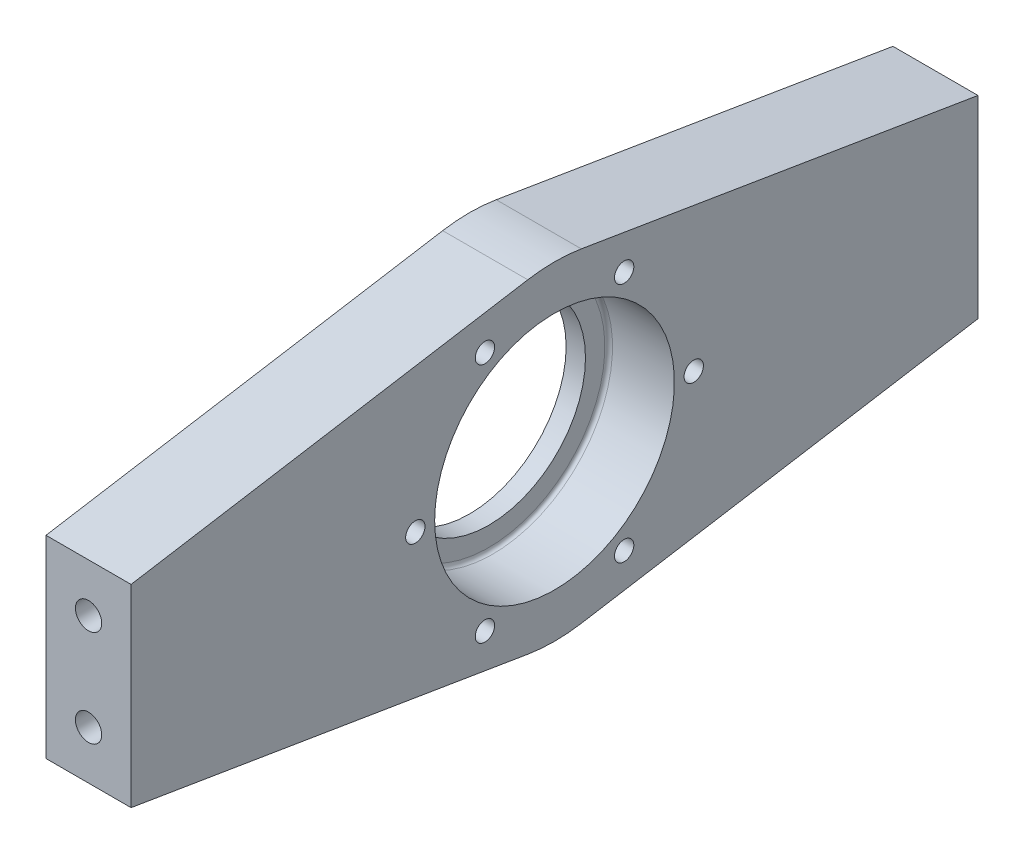
SolidWorks part; units mm, degrees
material "PA38 (3.3206)"
ref_plane "Płaszczyzna przednia" through (0, 0, 0) normal (0, 0, 1) x (1, 0, 0)
ref_plane "Płaszczyzna górna" through (0, 0, 0) normal (0, 1, 0) x (1, 0, 0)
ref_plane "Płaszczyzna prawa" through (0, 0, 0) normal (1, 0, 0) x (0, 0, -1)
sketch "Szkic1" plane through (0, 0, 0) normal (0, 0, 1) x (1, 0, 0)
  line L0 (-11, 0) -> (11, 0) construction
  line L1 (-11, 25) -> (-11, 42.5)
  line L2 (-11, 42.5) -> (11, 42.5)
  line L3 (11, 42.5) -> (11, 31)
  line L4 (11, 31) -> (-6, 31)
  line L5 (-6, 31) -> (-6, 25)
  line L6 (-6, 25) -> (-11, 25)
  dimension "D1" = 62
  dimension "D2" = 17
  dimension "D3" = 50
  dimension "D4" = 5
  dimension "D5" = 85
revolve "Obrót1" add sketch "Szkic1" angle 360 about L0
fillet "Zaokrąglenie1" radius 1 1 edges at (-6, 0, 31)
sketch "Szkic5" plane through (-11, 0, 0) normal (-1, 0, 0) x (0, 0, 1)
  line L0 (6.9218, 41.9326) -> (109.5, 25)
  line L1 (109.5, 25) -> (109.5, -25)
  line L2 (109.5, -25) -> (6.9218, -41.9326)
  line L3 (0, 42.5) -> (0, -42.5) construction
  circle A0 centre (0, 0) radius 42.5 construction
  circle A3 centre (0, 0) radius 42.5
  arc A4 (6.9218, -41.9326) -> (6.9218, 41.9326) centre (0, 0) ccw
  dimension "D1" = 50
  dimension "D2" = 219
  dimension "D3" = 0
extrude "Dodanie-wyciągnięcie1" add sketch "Szkic5" against normal up to surface (22 mm away) up to face at (11, 0, 42.5)
hole_wizard "Otwór gwintowany M81" positions "Szkic6" profile "Szkic8" tap size "M8" standard "DIN"
sketch "Szkic6" plane through (0, 0, 109.5) normal (0, 0, 1) x (1, 0, 0)
  line L0 (0, 12.5) -> (0, -12.5) construction
  point P0 (0, 12.5)
  point P2 (0, -12.5)
  dimension "D1" = 25
sketch "Szkic8" plane through (0, 12.5, 109.5) normal (1, 0, 0) x (0, -1, 0)
  line L0 (0, 0) -> (0, 24.2929)
  line L1 (0, 24.2929) -> (3.4, 22.25)
  line L2 (3.4, 22.25) -> (3.4, 0)
  line L5 (3.4, 0) -> (0, 0)
  line L10 (0, 24.2929) -> (-3.4, 22.25) construction
  line L11 (0, -6.35) -> (0, 107.95) construction
  dimension "Średnica wiertła gwintu" = 6.8
  dimension "Głębokość otworu gwintowanego" = 22.25
  dimension "Kąt wiertła" = 118
cosmetic thread "Gwint otworu2" parameters "D1"=16, "D2"=8
cosmetic thread "Gwint otworu3" parameters "D1"=16, "D2"=8
mirror "Lustro1" about plane through (0, 0, 0) normal (0, 0, 1) of "Otwór gwintowany M81", "Dodanie-wyciągnięcie1"
hole_wizard "Otwór gwintowany M61" positions "Szkic9" profile "Szkic10" tap size "M6" standard "DIN"
sketch "Szkic9" plane through (11, 0, 0) normal (1, 0, 0) x (0, 0, -1)
  line L0 (0, 0) -> (36, 0) construction
  point P0 (36, 0)
  dimension "D1" = 36
sketch "Szkic10" plane through (11, 0, -36) normal (0, 1, 0) x (0, 0, -1)
  line L0 (0, 0) -> (0, 18.5022)
  line L1 (0, 18.5022) -> (2.5, 17)
  line L2 (2.5, 17) -> (2.5, 0)
  line L5 (2.5, 0) -> (0, 0)
  line L10 (0, 18.5022) -> (-2.5, 17) construction
  line L11 (0, -6.35) -> (0, 107.95) construction
  dimension "Średnica wiertła gwintu" = 5
  dimension "Głębokość otworu gwintowanego" = 17
  dimension "Kąt wiertła" = 118
cosmetic thread "Gwint otworu4" parameters "D1"=12, "D2"=6
pattern_circular "Szyk kołowy1" count 6 over 360 about axis through (-11, 0, 0) along (-1, 0, 0) of "Otwór gwintowany M61"
